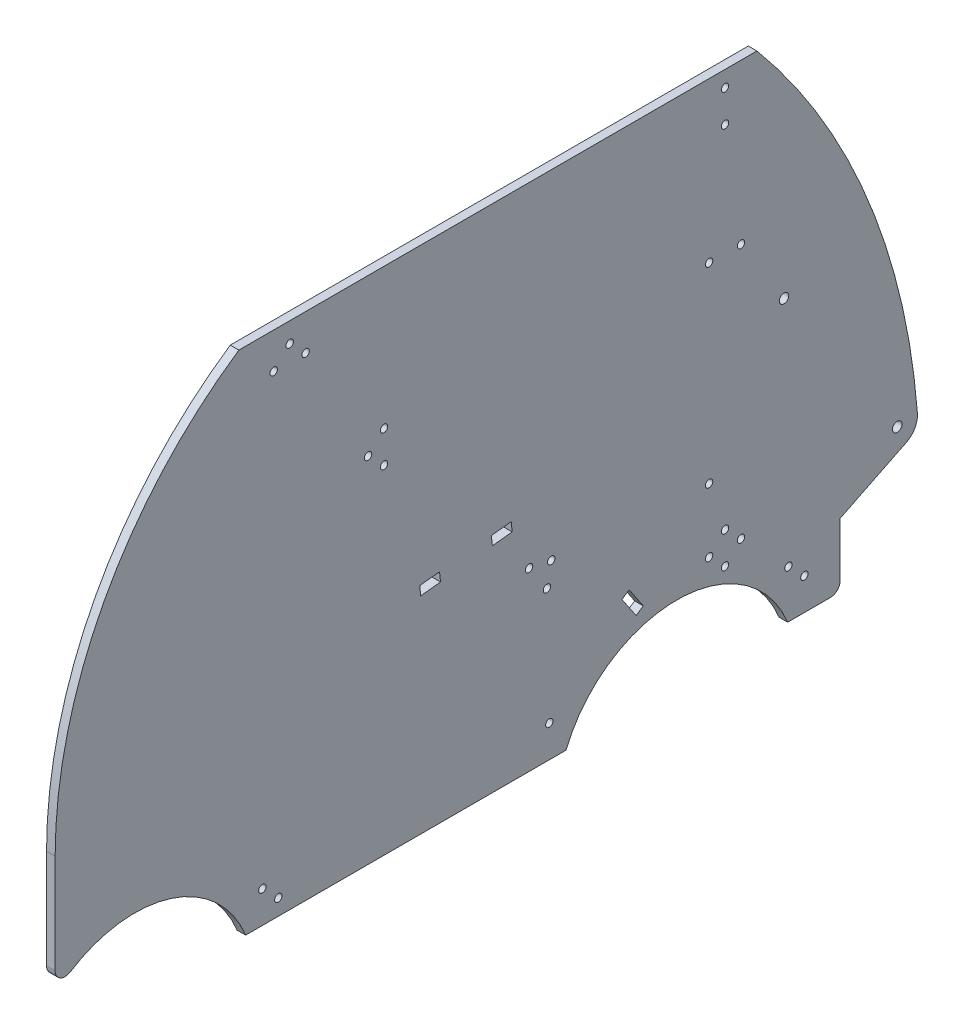
SolidWorks part; units mm, degrees
material "Acrylic (Medium-high impact)"
ref_plane "Front" through (0, 0, 0) normal (0, 0, 1) x (1, 0, 0)
ref_plane "Top" through (0, 0, 0) normal (0, 1, 0) x (1, 0, 0)
ref_plane "Right" through (0, 0, 0) normal (1, 0, 0) x (0, 0, -1)
ref_axis "side-side" through (80.9, 0, 0) along (-1, 0, 0)
ref_axis "up-down" through (0, 50, 0) along (0, -1, 0)
ref_axis "front-back" through (0, 0, -80.9) along (0, 0, 1)
sketch "Sketch2" plane through (0, 0, 0) normal (1, 0, 0) x (0, 0, -1)
  line L0 (290.8632, 48.3173) -> (257.7593, 32)
  line L1 (-40.6193, 0) -> (120.1378, 0)
  line L2 (-136.2407, 32.2723) -> (-136.2407, 82.1541)
  line L3 (-44.044, 256) -> (215.956, 256)
  line L4 (296.5313, 57.4304) -> (296.5313, 256) construction
  line L7 (258.4792, 32) -> (-136.2407, 32) construction
  line L8 (257.7593, 32) -> (257.7593, 5)
  line L9 (231.3807, 0) -> (252.7593, 0)
  line L10 (245.456, 256) -> (218.456, 256) construction
  line L11 (258.4792, 0) -> (-136.2407, 0) construction
  line L12 (-136.2407, 29.5) -> (-136.2407, 2.5) construction
  line L15 (215.956, 32) -> (215.956, 320) construction
  line L16 (148.2384, 51.4598) -> (151.8182, 53.8744) construction
  line L17 (155.3402, 40.931) -> (158.92, 43.3456) construction
  line L18 (155.3402, 40.931) -> (148.2384, 51.4598) construction
  line L19 (151.8182, 53.8744) -> (158.92, 43.3456) construction
  line L20 (148.2384, 51.4598) -> (151.8182, 53.8744)
  line L21 (155.3402, 40.931) -> (158.92, 43.3456)
  line L22 (155.3402, 40.931) -> (148.2384, 51.4598)
  line L23 (151.8182, 53.8744) -> (158.92, 43.3456)
  line L24 (46.7358, 108.2504) -> (56.681, 109.2956)
  line L25 (46.7358, 108.2504) -> (47.2294, 103.5539)
  line L26 (56.681, 109.2956) -> (57.1747, 104.5992)
  line L27 (47.2294, 103.5539) -> (57.1747, 104.5992)
  line L28 (82.6939, 112.0297) -> (92.6392, 113.075)
  line L29 (82.6939, 112.0297) -> (83.1876, 107.3332)
  line L30 (92.6392, 113.075) -> (93.1328, 108.3785)
  line L31 (83.1876, 107.3332) -> (93.1328, 108.3785)
  circle A0 centre (286.3713, 57.4304) radius 2.3813 construction
  circle A1 centre (286.3713, 57.4304) radius 2.3813
  arc A2 (290.8632, 48.3173) -> (296.5014, 58.2087) centre (286.3713, 57.4304) ccw
  circle A3 centre (247.7593, 16) radius 4 construction
  arc A4 (257.7593, 5) -> (252.7593, 0) centre (252.7593, 5) cw
  arc A5 (231.3807, 0) -> (120.1378, 0) centre (175.7593, -22.5) ccw
  circle A6 centre (175.7593, -22.5) radius 17 construction
  arc A7 (-40.6193, 0) -> (-128.5484, 28.059) centre (-96.2407, -22.5) ccw
  circle A8 centre (-96.2407, -22.5) radius 17 construction
  arc A9 (-128.5484, 28.059) -> (-136.2407, 32.2723) centre (-131.2407, 32.2723) cw
  arc A10 (296.5014, 58.2087) -> (215.956, 256) centre (-52.47, 31.3948) ccw
  arc A11 (-136.2407, 82.1541) -> (-44.044, 256) centre (73.7593, 82.1541) cw
  circle A12 centre (-10.544, 238) radius 1.85 construction
  circle A13 centre (-26.544, 238) radius 1.85 construction
  circle A14 centre (-18.544, 246) radius 1.85 construction
  circle A15 centre (-10.544, 238) radius 1.85
  circle A16 centre (-26.544, 238) radius 1.85
  circle A17 centre (-18.544, 246) radius 1.85
  circle A18 centre (199.956, 232) radius 1.85 construction
  circle A19 centre (199.956, 248) radius 1.85 construction
  circle A20 centre (199.956, 232) radius 1.85
  circle A21 centre (199.956, 248) radius 1.85
  circle A22 centre (207.956, 176) radius 1.85 construction
  circle A23 centre (207.956, 176) radius 1.85
  circle A24 centre (191.956, 80) radius 1.85 construction
  circle A25 centre (191.956, 80) radius 1.85
  circle A26 centre (199.956, 40) radius 1.85 construction
  circle A27 centre (199.956, 40) radius 1.85
  circle A28 centre (199.956, 56) radius 1.85 construction
  circle A29 centre (199.956, 56) radius 1.85
  circle A30 centre (207.956, 48) radius 1.85 construction
  circle A31 centre (207.956, 48) radius 1.85
  circle A32 centre (191.956, 48) radius 1.85 construction
  circle A33 centre (191.956, 48) radius 1.85
  circle A34 centre (231.7593, 24) radius 1.85 construction
  circle A35 centre (231.7593, 24) radius 1.85
  circle A36 centre (239.7593, 16) radius 1.85 construction
  circle A37 centre (239.7593, 16) radius 1.85
  circle A38 centre (111.7593, 16) radius 1.85 construction
  circle A39 centre (111.7593, 16) radius 1.85
  circle A40 centre (-32.2407, 16) radius 1.85 construction
  circle A41 centre (-32.2407, 16) radius 1.85
  circle A42 centre (-24.2407, 8) radius 1.85 construction
  circle A43 centre (-24.2407, 8) radius 1.85
  circle A44 centre (191.956, 176) radius 1.85 construction
  circle A45 centre (191.956, 176) radius 1.85
  circle A46 centre (110.5736, 75.111) radius 1.85 construction
  circle A47 centre (112.7323, 86.2169) radius 1.85 construction
  circle A48 centre (101.6265, 88.3756) radius 1.85 construction
  circle A49 centre (110.5736, 75.111) radius 1.85
  circle A50 centre (112.7323, 86.2169) radius 1.85
  circle A51 centre (101.6265, 88.3756) radius 1.85
  circle A52 centre (28.8202, 169.5) radius 1.85 construction
  circle A53 centre (28.8202, 185.5) radius 1.85 construction
  circle A54 centre (20.8202, 177.5) radius 1.85 construction
  circle A55 centre (28.8202, 169.5) radius 1.85
  circle A56 centre (28.8202, 185.5) radius 1.85
  circle A57 centre (20.8202, 177.5) radius 1.85
  circle A58 centre (229.5573, 141.6606) radius 2.3813 construction
  circle A59 centre (229.5573, 141.6606) radius 2.3813
  dimension "D1" = 10.16
  dimension "D2" = 10
  dimension "D3" = 5
  dimension "D4" = 120
  dimension "D5" = 5
  dimension "D6" = 350
  dimension "D7" = 210
  dimension "D8" = 260
extrude "Boss-Extrude1" add sketch "Sketch2" along normal blind 4.318
